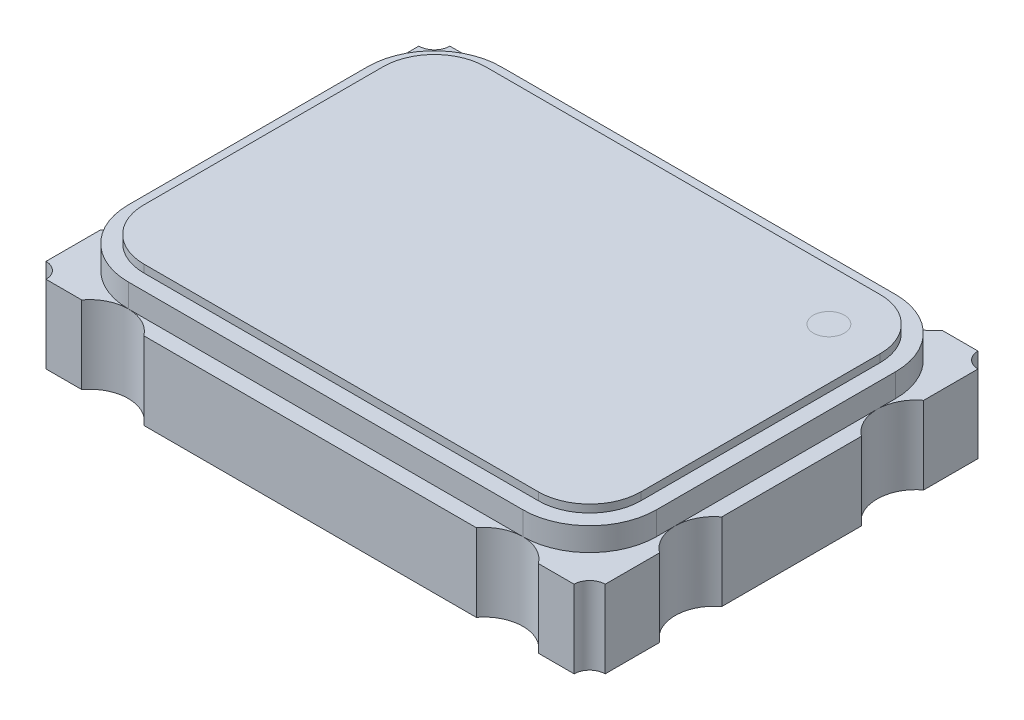
SolidWorks part; units mm, degrees
ref_plane "Спереди" through (0, 0, 0) normal (0, 0, 1) x (1, 0, 0)
ref_plane "Сверху" through (0, 0, 0) normal (0, 1, 0) x (1, 0, 0)
ref_plane "Справа" through (0, 0, 0) normal (1, 0, 0) x (0, 0, -1)
sketch "Эскиз1" plane through (0, 0, 0) normal (0, 1, 0) x (1, 0, 0)
  line L0 (-3.6, 0) -> (3.6, 0) construction
  line L1 (-3.4, 2.6) -> (-2.94, 2.6)
  line L2 (-3.6, 2.4) -> (-3.6, 1.7011)
  line L3 (-3.4, -2.6) -> (-2.94, -2.6)
  line L4 (3.6, 2.4) -> (3.6, 1.7011)
  line L5 (0, 2.6) -> (0, -2.6) construction
  line L6 (-2.14, 2.6) -> (2.14, 2.6)
  line L7 (2.94, 2.6) -> (3.4, 2.6)
  line L8 (-2.14, -2.6) -> (2.14, -2.6)
  line L9 (2.94, -2.6) -> (3.4, -2.6)
  line L10 (-3.6, 0.8989) -> (-3.6, -0.8989)
  line L11 (-3.6, -1.7011) -> (-3.6, -2.4)
  line L12 (3.6, 0.8989) -> (3.6, -0.8989)
  line L13 (3.6, -1.7011) -> (3.6, -2.4)
  arc A0 (-2.94, 2.6) -> (-2.14, 2.6) centre (-2.54, 2.9) ccw
  arc A1 (-2.94, -2.6) -> (-2.14, -2.6) centre (-2.54, -2.9) cw
  arc A2 (2.94, -2.6) -> (2.14, -2.6) centre (2.54, -2.9) ccw
  arc A3 (2.94, 2.6) -> (2.14, 2.6) centre (2.54, 2.9) cw
  arc A4 (-3.6, 0.8989) -> (-3.6, 1.7011) centre (-3.9022, 1.3) ccw
  arc A5 (-3.6, -0.8989) -> (-3.6, -1.7011) centre (-3.9022, -1.3) cw
  arc A6 (3.6, -0.8989) -> (3.6, -1.7011) centre (3.9022, -1.3) ccw
  arc A7 (3.6, 0.8989) -> (3.6, 1.7011) centre (3.9022, 1.3) cw
  arc A8 (-3.4, 2.6) -> (-3.6, 2.4) centre (-3.6, 2.6) cw
  arc A9 (-3.4, -2.6) -> (-3.6, -2.4) centre (-3.6, -2.6) ccw
  arc A10 (3.4, -2.6) -> (3.6, -2.4) centre (3.6, -2.6) cw
  arc A11 (3.4, 2.6) -> (3.6, 2.4) centre (3.6, 2.6) ccw
  point P12 (-2.54, 2.4)
  point P27 (-3.4, 1.3)
  point P43 (3.6, 0)
  point P44 (-3.6, 0)
  dimension "D4" = 0.2
  dimension "D5" = 0.5
  dimension "D8" = 0.5022
  dimension "D6" = 0.2
  dimension "D1" = 7.2
  dimension "D2" = 5.2
  dimension "D3" = 2.54
  dimension "D7" = 2.54
  dimension "D9" = 0.2
  dimension "D10" = 1.3
extrude "Бобышка-Вытянуть1" add sketch "Эскиз1" along normal blind 1
sketch "Эскиз2" plane through (0, 1, 0) normal (0, 1, 0) x (1, 0, 0)
  line L1 (-2.54, 2.4) -> (2.54, 2.4)
  line L2 (-3.4, 1.54) -> (-3.4, -1.54)
  line L3 (-2.54, -2.4) -> (2.54, -2.4)
  line L4 (3.4, 1.54) -> (3.4, -1.54)
  arc A0 (-3.6, 0.8989) -> (-3.6, 1.7011) centre (-3.9022, 1.3) ccw construction
  arc A1 (-2.94, 2.6) -> (-2.14, 2.6) centre (-2.54, 2.9) ccw construction
  arc A2 (2.54, -2.4) -> (3.4, -1.54) centre (2.54, -1.54) ccw
  arc A3 (-3.4, -1.54) -> (-2.54, -2.4) centre (-2.54, -1.54) ccw
  arc A4 (2.54, 2.4) -> (3.4, 1.54) centre (2.54, 1.54) cw
  arc A5 (-2.54, 2.4) -> (-3.4, 1.54) centre (-2.54, 1.54) ccw
  point P4 (0, 2.4)
  point P6 (-3.4, 0)
  point P10 (-3.4, 1.3)
  point P14 (-2.54, 2.4)
  point P23 (0, 0)
extrude "Бобышка-Вытянуть2" add sketch "Эскиз2" along normal blind 0.3
sketch "Эскиз3" plane through (0, 1.3, 0) normal (0, 1, 0) x (1, 0, 0)
  line L8 (3.2, -1.54) -> (3.2, 1.54)
  line L9 (2.54, 2.2) -> (-2.54, 2.2)
  line L10 (-3.2, 1.54) -> (-3.2, -1.54)
  line L11 (-2.54, -2.2) -> (2.54, -2.2)
  line L12 (3.2, -1.54) -> (3.2, 1.54)
  line L13 (2.54, 2.2) -> (-2.54, 2.2)
  line L14 (-3.2, 1.54) -> (-3.2, -1.54)
  line L15 (-2.54, -2.2) -> (2.54, -2.2)
  arc A8 (2.54, -2.2) -> (3.2, -1.54) centre (2.54, -1.54) ccw
  arc A9 (3.2, 1.54) -> (2.54, 2.2) centre (2.54, 1.54) ccw
  arc A10 (-2.54, 2.2) -> (-3.2, 1.54) centre (-2.54, 1.54) ccw
  arc A11 (-3.2, -1.54) -> (-2.54, -2.2) centre (-2.54, -1.54) ccw
  arc A12 (2.54, -2.2) -> (3.2, -1.54) centre (2.54, -1.54) ccw
  arc A13 (3.2, 1.54) -> (2.54, 2.2) centre (2.54, 1.54) ccw
  arc A14 (-2.54, 2.2) -> (-3.2, 1.54) centre (-2.54, 1.54) ccw
  arc A15 (-3.2, -1.54) -> (-2.54, -2.2) centre (-2.54, -1.54) ccw
  dimension "D1" = 0.2
extrude "Бобышка-Вытянуть3" add sketch "Эскиз3" along normal blind 0.1
sketch "Эскиз4" plane through (0, 0, 0) normal (0, -1, 0) x (1, 0, 0)
  line L0 (4.6894, 0) -> (-5.0827, 0) construction
  line L1 (3.24, 2.5) -> (1.84, 2.5)
  line L2 (3.24, 2.5) -> (3.24, 1.3)
  line L3 (3.24, 1.3) -> (1.84, 1.3)
  line L4 (1.84, 2.5) -> (1.84, 1.3)
  line L5 (0, 4.8218) -> (0, -5.3293) construction
  line L6 (-1.84, 2.5) -> (-1.84, 1.3)
  line L7 (-3.24, 2.5) -> (-1.84, 2.5)
  line L8 (-3.24, 1.3) -> (-1.84, 1.3)
  line L9 (-3.24, 2.5) -> (-3.24, 1.3)
  line L10 (-3.24, -2.5) -> (-3.24, -1.3)
  line L11 (-3.24, -1.3) -> (-1.84, -1.3)
  line L12 (-1.84, -2.5) -> (-1.84, -1.3)
  line L13 (-3.24, -2.5) -> (-1.84, -2.5)
  line L14 (3.24, -1.3) -> (2.34, -1.3)
  line L15 (3.24, -1.3) -> (3.24, -2.5)
  line L16 (3.24, -2.5) -> (1.84, -2.5)
  line L17 (1.84, -1.8) -> (1.84, -2.5)
  line L18 (2.34, -1.3) -> (1.84, -1.8)
  point P4 (2.54, 2.5)
  dimension "D1" = 1.2
  dimension "D2" = 1.4
  dimension "D3" = 2.54
  dimension "D4" = 1.3
  dimension "D5" = 1.3
  dimension "D6" = 45
  dimension "D7" = 0.5
wrap "Перенос4" sketch "Эскиз4" wrap type scribe source sketch "Эскиз4"
sketch "Эскиз6" plane through (0, 1.4, 0) normal (0, 1, 0) x (1, 0, 0)
  circle A0 centre (2.54, 1.54) radius 0.2
  arc A1 (3.2, 1.54) -> (2.54, 2.2) centre (2.54, 1.54) ccw construction
  dimension "D1" = 0.4
wrap "Перенос5" sketch "Эскиз6" wrap type scribe source sketch "Эскиз6"
